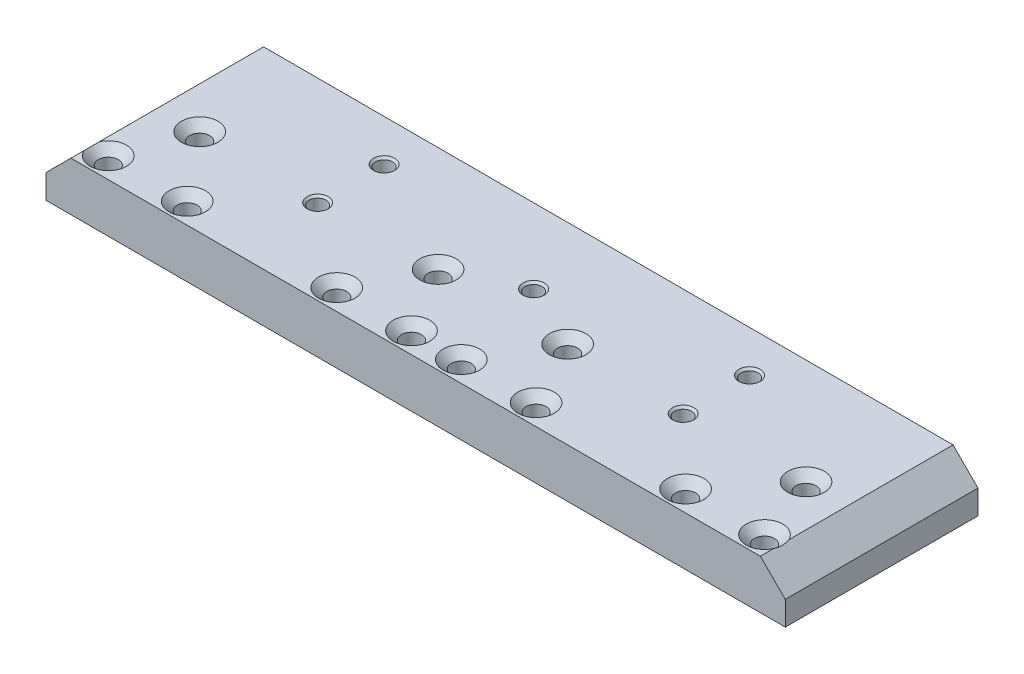
SolidWorks part; units mm, degrees
material "6061-T6 (SS)"
ref_plane "Front Plane" through (0, 0, 0) normal (0, 0, 1) x (1, 0, 0)
ref_plane "Top Plane" through (0, 0, 0) normal (0, 1, 0) x (1, 0, 0)
ref_plane "Right Plane" through (0, 0, 0) normal (1, 0, 0) x (0, 0, -1)
sketch "Sketch1" plane through (0, 0, 0) normal (0, 1, 0) x (1, 0, 0)
  line L1 (44.5, -11.6) -> (-44.5, -11.6)
  line L2 (44.5, -11.6) -> (44.5, 11.6)
  line L3 (44.5, 11.6) -> (-44.5, 11.6)
  line L4 (-44.5, -11.6) -> (-44.5, 11.6)
  line L5 (44.5, -11.6) -> (-44.5, 11.6) construction
  line L6 (44.5, 11.6) -> (-44.5, -11.6) construction
  point P0 (0, 0)
  dimension "D1" = 89
  dimension "D2" = 23.2
extrude "Boss-Extrude1" add sketch "Sketch1" along normal blind 4 and the other way blind 1.9
hole_wizard "M2.5x0.45 Tapped Hole2" positions "Sketch4" profile "Sketch5" tap size "M2.5x0.45" standard "ANSI Metric" end condition through all
sketch "Sketch4" plane through (0, 4, 0) normal (0, 1, 0) x (1, 0, 0)
  line L0 (44.5, 11.6) -> (-44.5, 11.6) construction
  point P0 (-22, 6.6)
  point P2 (-22, -1.4)
  point P4 (22, -1.4)
  point P6 (22, 6.6)
  point P8 (0, 2.6)
  dimension "D1" = 8
  dimension "D2" = 8
  dimension "D3" = 44
  dimension "D4" = 22
  dimension "D5" = 9
  dimension "D6" = 4
  dimension "D7" = 4
cosmetic thread "Hole Thread6" parameters "D2"=2.5
cosmetic thread "Hole Thread7" parameters "D2"=2.5
cosmetic thread "Hole Thread8" parameters "D2"=2.5
cosmetic thread "Hole Thread9" parameters "D2"=2.5
cosmetic thread "Hole Thread10" parameters "D2"=2.5
sketch "Sketch5" plane through (-22, 4, -6.6) normal (1, 0, 0) x (0, 0, 1)
  line L0 (0, 0) -> (0, 5.9)
  line L1 (0, 5.9) -> (1.025, 5.9)
  line L2 (1.025, 5.9) -> (1.025, 0.25)
  line L3 (1.025, 0.25) -> (1.275, 0)
  line L5 (1.275, 0) -> (0, 0)
  line L6 (-1.025, 0.25) -> (-1.275, 0) construction
  line L11 (0, -6.35) -> (0, 107.95) construction
  dimension "Thru Tap Drill Dia." = 2.05
  dimension "Thru Tap Drill Depth" = 5.9
  dimension "Near C'Sink Dia." = 2.55
  dimension "Near C'Sink Angle" = 90
hole_wizard "CSK for M2 Flat Head Machine Screw1" positions "Sketch6" profile "Sketch7" countersink size "M2" standard "ANSI Metric"
sketch "Sketch6" plane through (0, 4, 0) normal (0, 1, 0) x (1, 0, 0)
  line L0 (-44.5, -11.6) -> (44.5, -11.6) construction
  line L1 (-39.5, -9.1) -> (-30, -9.1) construction
  line L2 (-30, -9.1) -> (30, -9.1) construction
  line L3 (30, -9.1) -> (39.5, -9.1) construction
  line L5 (0, 0) -> (0, -11.6) construction
  line L7 (-7.8, -9.1) -> (-7.8, -1.1) construction
  circle A0 centre (0, 2.6) radius 1.025 construction
  point P0 (-36.5, -1.1)
  point P2 (-39.5, -9.1)
  point P4 (-30, -9.1)
  point P6 (30, -9.1)
  point P8 (39.5, -9.1)
  point P10 (36.5, -1.1)
  point P41 (-3, -9.1)
  point P43 (-12, -9.1)
  point P47 (12, -9.1)
  point P48 (3, -9.1)
  point P64 (-7.8, -1.1)
  point P66 (7.8, -1.1)
  dimension "D5" = 39.5
  dimension "D1" = 39.5
  dimension "D2" = 3
  dimension "D3" = 8
  dimension "D4" = 9.5
  dimension "D6" = 3
  dimension "D7" = 9.5
  dimension "D8" = 8
  dimension "D9" = 2.5
  dimension "D10" = 2.5
  dimension "D11" = 9
  dimension "D12" = 6
  dimension "D13" = 4.2
  dimension "D14" = 8
sketch "Sketch7" plane through (-36.5, 4, 1.1) normal (1, 0, 0) x (0, 0, 1)
  line L0 (0, 0) -> (0, 7.171)
  line L1 (0, 7.171) -> (1.2, 6.45)
  line L2 (1.2, 6.45) -> (1.2, 1)
  line L3 (1.2, 1) -> (2.2, 0)
  line L5 (2.2, 0) -> (0, 0)
  line L6 (-1.2, 1) -> (-2.2, 0) construction
  line L10 (0, 7.171) -> (-1.2, 6.45) construction
  line L11 (0, -6.35) -> (0, 107.95) construction
  dimension "Hole Dia." = 2.4
  dimension "Hole Depth" = 6.45
  dimension "Near C'Sink Dia." = 4.4
  dimension "Near C'Sink Angle" = 90
  dimension "Drill Angle" = 118
sketch "Sketch8" plane through (0, 0, 11.6) normal (0, 0, 1) x (1, 0, 0)
  line L9 (41.5, 4) -> (44.5, 4)
  line L10 (-44.5, 4) -> (44.5, 4) construction
  line L11 (44.5, 4) -> (44.5, 1)
  line L12 (44.5, 4) -> (44.5, -1.9) construction
  line L13 (44.5, 1) -> (41.5, 4)
  line L14 (-44.5, 4) -> (-44.5, 1)
  line L15 (-44.5, 4) -> (-44.5, -1.9) construction
  line L16 (-44.5, 1) -> (-41.5, 4)
  line L17 (-41.5, 4) -> (-44.5, 4)
  dimension "D1" = 3
  dimension "D2" = 2.9
  dimension "D3" = 2.9
  dimension "D4" = 3
extrude "Cut-Extrude1" cut sketch "Sketch8" against normal up to surface (23.2 mm away) up to face at (0, 1.05, -11.6)
